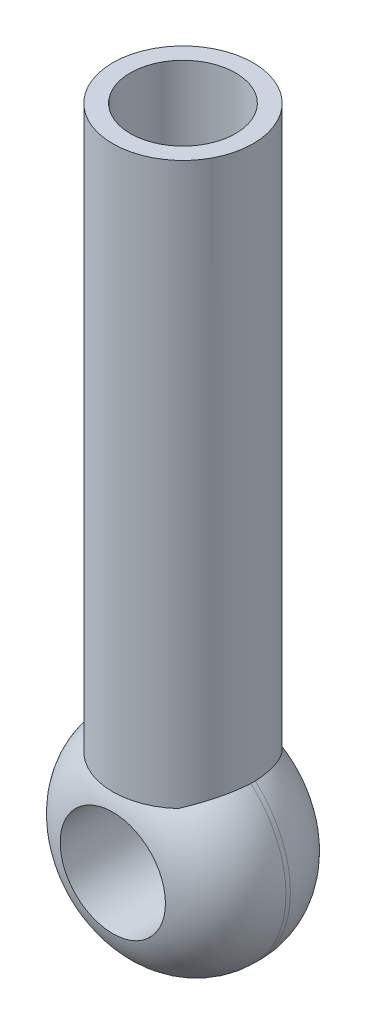
SolidWorks part; units mm, degrees
ref_plane "Front Plane" through (0, 0, 0) normal (0, 0, 1) x (1, 0, 0)
ref_plane "Top Plane" through (0, 0, 0) normal (0, 1, 0) x (1, 0, 0)
ref_plane "Right Plane" through (0, 0, 0) normal (1, 0, 0) x (0, 0, -1)
sketch "Sketch1" plane through (0, 0, 0) normal (0, 0, 1) x (1, 0, 0)
  circle A0 centre (0, 0) radius 7.5
  circle A1 centre (0, 0) radius 15
  dimension "D1" = 15
  dimension "D2" = 30
extrude "Boss-Extrude1" add sketch "Sketch1" along normal blind 20
fillet "Fillet1" radius 10 2 edges at (15, 0, 0) (15, 0, 20)
sketch "Sketch2" plane through (0, 0, 0) normal (0, 1, 0) x (1, 0, 0)
  circle A0 centre (0, -10) radius 10
  dimension "D1" = 20
  dimension "D2" = 10
extrude "Boss-Extrude2" add sketch "Sketch2" along normal blind 80 from offset 10
sketch "Sketch3" plane through (0, 90, 0) normal (0, 1, 0) x (1, 0, 0)
  circle A0 centre (0, -10) radius 7.5
  dimension "D1" = 15
extrude "Cut-Extrude1" cut sketch "Sketch3" against normal blind 40
